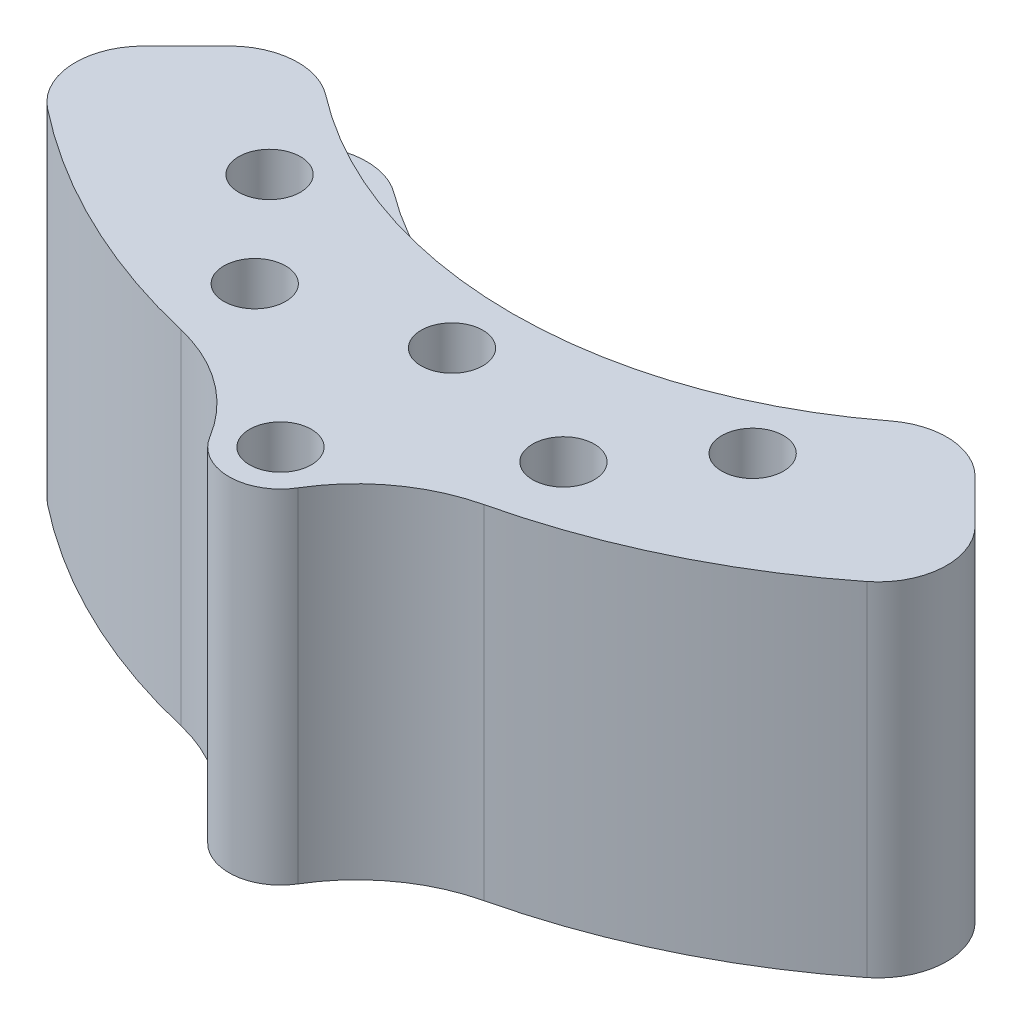
SolidWorks part; units mm, degrees
ref_plane "Front Plane" through (0, 0, 0) normal (0, 0, 1) x (1, 0, 0)
ref_plane "Top Plane" through (0, 0, 0) normal (0, 1, 0) x (1, 0, 0)
ref_plane "Right Plane" through (0, 0, 0) normal (1, 0, 0) x (0, 0, -1)
sketch "Sketch1" plane through (0, 0, 0) normal (0, 1, 0) x (1, 0, 0)
  line L2 (-21.7322, -21.7322) -> (-34.574, -34.574)
  line L3 (0, 0) -> (0, -48.895) construction
  line L5 (21.7322, -21.7322) -> (34.574, -34.574)
  arc A0 (-21.7322, -21.7322) -> (21.7322, -21.7322) centre (0, 0) ccw
  arc A1 (-34.574, -34.574) -> (34.574, -34.574) centre (0, 0) ccw
  circle A2 centre (-17.8858, -34.3584) radius 2.286
  circle A3 centre (0, -38.735) radius 2.286
  circle A4 centre (17.8858, -34.3584) radius 2.286
  dimension "D1" = 97.79
  dimension "D2" = 30.734
  dimension "D4" = 4.572
  dimension "D3" = 45
extrude "Boss-Extrude1" add sketch "Sketch1" along normal blind 25.4
sketch "Sketch2" plane through (0, 25.4, 0) normal (0, 1, 0) x (1, 0, 0)
  circle A0 centre (0, 0) radius 34.29
  dimension "D1" = 68.58
extrude "Cut-Extrude1" cut sketch "Sketch2" against normal blind 6.35
fillet "Fillet1" radius 5.08 4 edges at (34.574, 12.7, 34.574) (21.7322, 9.525, 21.7322) (-34.574, 12.7, 34.574) (-21.7322, 9.525, 21.7322)
fillet "Fillet2" radius 5.08 2 edges at (-24.1512, 22.225, 24.3418) (24.1512, 22.225, 24.3418)
fillet "Fillet3" radius 1.27 3 edges at (-24.3424, 19.05, 26.1288) (24.3424, 19.05, 26.1288) (0, 19.05, 34.29)
sketch "Sketch3" plane through (0, 25.4, 0) normal (0, 1, 0) x (1, 0, 0)
  line L0 (0, 0) -> (0, -48.895) construction
  circle A0 centre (11.43, -41.91) radius 2.286
  arc A2 (-30.3322, -38.3494) -> (30.3322, -38.3494) centre (0, 0) ccw construction
  circle A3 centre (-11.43, -41.91) radius 2.286
  dimension "D3" = 4.572
  dimension "D1" = 41.91
  dimension "D2" = 11.43
extrude "Cut-Extrude2" cut sketch "Sketch3" against normal through all
sketch "Sketch4" plane through (0, 25.4, 0) normal (0, 1, 0) x (1, 0, 0)
  arc A0 (-2.7677, -48.8166) -> (2.7677, -48.8166) centre (0, 0) ccw
  circle A1 centre (0, -51.435) radius 2.286
  arc A2 (-2.7677, -48.8166) -> (2.7677, -48.8166) centre (0, -51.435) ccw
  arc A3 (-30.3322, -38.3494) -> (30.3322, -38.3494) centre (0, 0) ccw construction
  dimension "D2" = 4.572
  dimension "D3" = 7.62
  dimension "D1" = 51.435
extrude "Boss-Extrude2" add sketch "Sketch4" against normal up to surface (25.4 mm away) up to face at (11.43, 0, 44.196)
fillet "Fillet4" radius 12.7 2 edges at (2.7677, 12.7, 48.8166) (-2.7677, 12.7, 48.8166)
